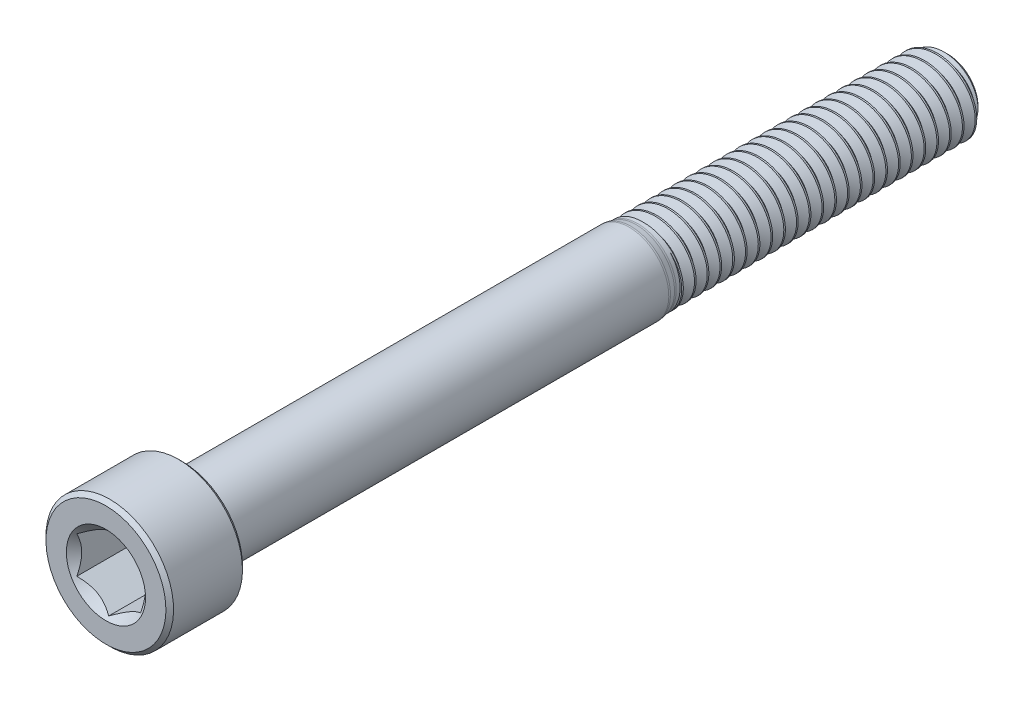
SolidWorks part; units mm, degrees
ref_plane "Front Plane" through (0, 0, 0) normal (0, 0, 1) x (1, 0, 0)
ref_plane "Top Plane" through (0, 0, 0) normal (0, 1, 0) x (1, 0, 0)
ref_plane "Right Plane" through (0, 0, 0) normal (1, 0, 0) x (0, 0, -1)
sketch "Sketch1" plane through (0, 0, 0) normal (1, 0, 0) x (0, 0, -1)
  line L0 (-33, 0) -> (33, 0) construction
  line L1 (33, 0) -> (33, 2.3505) construction
  line L2 (33, 2.3505) -> (32.3505, 3) construction
  line L3 (32.3505, 3) -> (32.25, 3) construction
  line L4 (32.25, 3) -> (-27, 3) construction
  line L5 (-27, 3) -> (-27, 5) construction
  line L6 (-27, 5) -> (-33, 5) construction
  line L7 (-33, 5) -> (-33, 0) construction
  line L8 (33, 2.3505) -> (33, 3) construction
  line L9 (32.9375, 3.1083) -> (33.4375, 2.2422) construction
  line L10 (33.4375, 2.2422) -> (33.9375, 3.1083) construction
  line L11 (33.9375, 3.1083) -> (32.9375, 3.1083) construction
  line L12 (33.4375, 3.1083) -> (33.4375, 3) construction
  line L13 (33.4375, 2.2422) -> (33.4375, 2.3505) construction
  line L14 (33.375, 2.3505) -> (33.5, 2.3505) construction
  line L15 (33, 3) -> (33.875, 3) construction
  line L16 (32.9688, 3.0541) -> (33.9063, 3.0541) construction
  line L17 (33, 0) -> (33, -3) construction
  line L18 (-27.3, 5) -> (-27, 4.7) construction
  line L19 (-32.7, 5) -> (-33, 4.7) construction
  line L20 (-27, 3) -> (-27, 0) construction
  line L21 (-27, 1.5) -> (-7, 1.5) construction
  line L22 (-7, 1.5) -> (13, 1.5) construction
  line L23 (13, 1.5) -> (33, 1.5) construction
  line L24 (-7, 1.5) -> (-7, 3) construction
  line L25 (-7, 3) -> (-7, 5) construction
  line L26 (13, 1.5) -> (13, 5) construction
  point P0 (-33, 2.5)
  point P3 (30.5, 3)
  point P4 (0, 0)
  point P18 (13, 3)
  point P22 (33.4375, 2.3505)
  point P24 (32.25, 3)
  point P25 (33.4375, 3)
  point P28 (33.4375, 3.0541)
  point P29 (30.5, -3)
  point P30 (-7, 3)
  point P31 (-30, 5)
  point P37 (-28.05, 5)
  point P38 (-32.55, 5)
  point P45 (-7, 1.5)
  point P46 (13, 1.5)
  point P49 (9, 3)
  dimension "D1" = 45
  dimension "D2" = 0.125
  dimension "D7" = 0.3
  dimension "D8" = 0.3
  dimension "D9" = 0.3
  dimension "D10" = 0.15
  dimension "D11" = 0.75
  dimension "Drive Size" = 5
  dimension "Head Diameter" = 10
  dimension "Head Height" = 6
  dimension "Thread Pitch" = 1
  dimension "Thread Dia" = 6
  dimension "Length" = 60
  dimension "D12" = 0.75
  dimension "D4" = 2.5
  dimension "Minimum Thread Length" = 24
  dimension "D3" = 36
sketch "Sketch2" plane through (0, 0, 0) normal (1, 0, 0) x (0, 0, -1)
  line L0 (-33, 0) -> (-33, 4.7)
  line L1 (-32.7, 5) -> (-27.3, 5)
  line L2 (-27, 4.7) -> (-27, 3.4083)
  line L4 (32.3505, 3) -> (33, 2.3505)
  line L5 (33, 2.3505) -> (33, 0)
  line L6 (-27, 5) -> (-33, 5) construction
  line L7 (33, 0) -> (-33, 0)
  line L8 (-32.7, 5) -> (-33, 4.7) construction
  line L10 (-32.7, 5) -> (-33, 4.7)
  line L14 (-27.3, 5) -> (-27, 4.7) construction
  line L16 (-27.3, 5) -> (-27, 4.7)
  line L17 (-27, 3) -> (-27, 5) construction
  line L18 (-26.7, 3.1083) -> (8.0069, 3.1083)
  line L19 (8.6989, 3) -> (32.3505, 3)
  line L20 (32.25, 3) -> (-27, 3) construction
  line L21 (8.1532, 3.0938) -> (8.5526, 3.0144)
  line L22 (33.9375, 3.1083) -> (32.9375, 3.1083) construction
  arc A1 (-27, 3.4083) -> (-26.7, 3.1083) centre (-26.7, 3.4083) ccw
  arc A2 (8.0069, 3.1083) -> (8.1532, 3.0938) centre (8.0069, 2.3583) cw
  arc A3 (8.5526, 3.0144) -> (8.6989, 3) centre (8.6989, 3.75) ccw
  point P39 (8.625, 3)
  dimension "D3" = 0.3
  dimension "D6" = 0.75
  dimension "D4" = 11.25
  dimension "D5" = 0.375
revolve "Revolve1" add sketch "Sketch2" angle 360 about L7
sketch "Sketch3" plane through (0, 0, 33) normal (0, 0, 1) x (1, 0, 0)
  line L1 (2.5, -1.4434) -> (2.5, 1.4434)
  line L2 (2.5, 1.4434) -> (0, 2.8868)
  line L3 (0, 2.8868) -> (-2.5, 1.4434)
  line L4 (-2.5, 1.4434) -> (-2.5, -1.4434)
  line L5 (-2.5, -1.4434) -> (0, -2.8868)
  line L6 (0, -2.8868) -> (2.5, -1.4434)
  circle A0 centre (0, 0) radius 2.5 construction
  circle A1 centre (0, 0) radius 5 construction
  circle A2 centre (0, 0) radius 5 construction
  circle A3 centre (0, 0) radius 2.8868 construction
  dimension "D1" = 5.7735
extrude "Cut-Extrude1" cut sketch "Sketch3" against normal offset from surface (5 mm away) 1 up to face at (0, 4.7, 27)
sketch "Sketch4" plane through (0, 0, 33) normal (0, 0, 1) x (1, 0, 0)
  circle A0 centre (0, 0) radius 3.1033
  dimension "D1" = 6.2065
extrude "Cut-Extrude2" cut sketch "Sketch4" against normal up to vertex (3 mm away) draft 45 up to point (0, 5, 30)
sketch "Sketch11" plane through (0, 0, 0) normal (1, 0, 0) x (0, 0, -1)
  line L0 (-33, 0) -> (33, 0) construction
  line L1 (-33, 0) -> (33, 0) construction
  line L2 (-23.85, 0) -> (-23.85, 3) construction
  line L3 (32.25, 3) -> (-27, 3) construction
  line L4 (4.8569, 0) -> (4.8569, 3) construction
  point P2 (-23.85, 0)
  point P3 (4.8569, 0)
  dimension "D1" = 3.15
  dimension "D2" = 3.15
sketch "Sketch6" plane through (0, 0, -33) normal (0, 0, -1) x (-1, 0, 0)
  circle A0 centre (0, 0) radius 3
curve "Helix/Spiral1" pitch 1 height 25 radius 3 centre (0, 0, -33) axis (0, 0, 1) start towards (0, 1, 0)
sketch "Sketch10" plane through (0, 0, 0) normal (1, 0, 0) x (0, 0, -1)
  line L0 (9, -3) -> (9, 3)
  line L2 (-33, 0) -> (33, 0) construction
  point P3 (9, 0)
split "Split1" trim tools "Sketch10" bodies to split 106 resulting bodies 114 115
sketch "Sketch7" plane through (0, 0, 0) normal (1, 0, 0) x (0, 0, -1)
  line L0 (32.9688, 3.0541) -> (33.9063, 3.0541)
  line L1 (33.9063, 3.0541) -> (33.5, 2.3505)
  line L2 (33.5, 2.3505) -> (33.375, 2.3505)
  line L3 (33.375, 2.3505) -> (32.9688, 3.0541)
sweep "Cut-Sweep1" cut profiles "Sketch7" path "Helix/Spiral1" align with end faces yes
sketch "Sketch8" plane through (0, 0, 0) normal (1, 0, 0) x (0, 0, -1)
  line L0 (-27, 0) -> (-27, 3)
  line L2 (-27, 3) -> (9, 3)
  line L4 (9, 3) -> (10.7321, 0)
  line L5 (10.7321, 0) -> (-27, 0)
  line L6 (32.25, 3) -> (-27, 3) construction
  line L7 (-33, 0) -> (33, 0) construction
  dimension "D1" = 60
  dimension "D2" = 24
revolve "Revolve2" add sketch "Sketch8" angle 360 about L5
equation "\"D2@Sketch1\" = \"Thread Pitch@Sketch1\" / 8"
equation "\"D4@Helix/Spiral1\" = \"Thread Pitch@Sketch1\""
equation "\"D7@Sketch1\" = \"Head Height@Sketch1\" * .05"
equation "\"D8@Sketch1\"=\"D7@Sketch1\""
equation "\"D9@Sketch1\"=\"D7@Sketch1\""
equation "\"D10@Sketch1\"=\"D7@Sketch1\"/2"
equation "\"D11@Sketch1\"=\"D10@Sketch1\"*5"
equation "\"D4@Sketch1\"=\"Thread Pitch@Sketch1\"*2.5"
equation "\"D12@Sketch1\"=\"Thread Pitch@Sketch1\"*.75"
equation "\"D3@Helix/Spiral1\"=\"Minimum Thread Length@Sketch1\"+\"Thread Pitch@Sketch1\""
equation "\"D2@Sketch8\"=\"Minimum Thread Length@Sketch1\""
equation "\"D3@Sketch2\"=\"Thread Dia@Sketch1\"*0.05"
equation "\"D5@Sketch2\"=\"D12@Sketch1\"*0.5"
equation "\"D6@Sketch2\"=\"Thread Dia@Sketch1\"*0.125"
equation "\"D1@Sketch11\"=\"D3@Sketch1\"*0.0875"
equation "\"D2@Sketch11\"=\"D1@Sketch11\""
equation "\"D1@Sketch4\"=\"D1@Sketch3\"*1.075"
